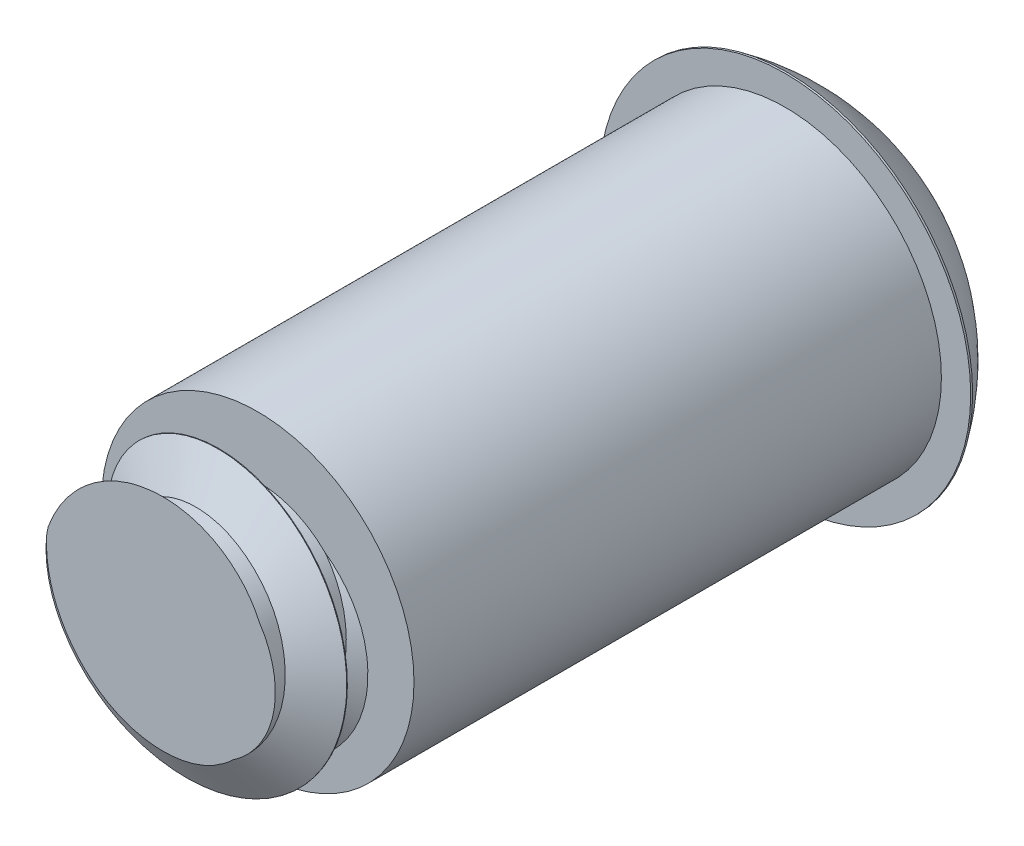
SolidWorks part; units mm, degrees
ref_plane "Front Plane" through (0, 0, 0) normal (0, 0, 1) x (1, 0, 0)
ref_plane "Top Plane" through (0, 0, 0) normal (0, 1, 0) x (1, 0, 0)
ref_plane "Right Plane" through (0, 0, 0) normal (1, 0, 0) x (0, 0, -1)
sketch "Sketch1" plane through (0, 0, 0) normal (0, 0, 1) x (1, 0, 0)
  circle A0 centre (0, 0) radius 1.7526
curve "Helix/Spiral1" pitch 0.7937 height 1.524 radius 1.7526 left hand yes centre (0, 0, 0) axis (0, 0, 1) start towards (0, 1, 0)
sketch "Sketch2" plane through (0, 0, 0) normal (0, 0, 1) x (1, 0, 0)
  circle A0 centre (0, 0) radius 1.7526
extrude "Boss-Extrude1" add sketch "Sketch2" along normal blind 1.016
sketch "Sketch3" plane through (0, 0, 0) normal (1, 0, 0) x (0, 0, -1)
  line L0 (-0.3925, 1.7526) -> (-0.0992, 1.2446)
  line L1 (-0.0992, 1.2446) -> (0.0992, 1.2446)
  line L2 (0.0992, 1.2446) -> (0.3925, 1.7526)
  line L3 (0.3925, 1.7526) -> (-0.3925, 1.7526)
  line L4 (0, 1.7526) -> (0, 1.2446) construction
  dimension "D1" = 60
  dimension "D2" = 0.508
  dimension "D3" = 0.1984
sweep "Cut-Sweep1" cut profiles "Sketch3" path "Helix/Spiral1" align with end faces yes
sketch "Sketch4" plane through (0, 0, 0) normal (0, 0, 1) x (1, 0, 0)
  circle A0 centre (0, 0) radius 2.032
extrude "Boss-Extrude2" add sketch "Sketch4" against normal blind 6.858
sketch "Sketch5" plane through (0, 0, -6.858) normal (0, 0, -1) x (-1, 0, 0)
  circle A0 centre (0, 0) radius 2.413
extrude "Boss-Extrude3" add sketch "Sketch5" along normal blind 0.0254
dome "Dome1" faces to dome 1 distance 1.27 reverse direction no elliptical dome no face at (-2.413, 0, -6.8834) parameters "D1"=1.27
